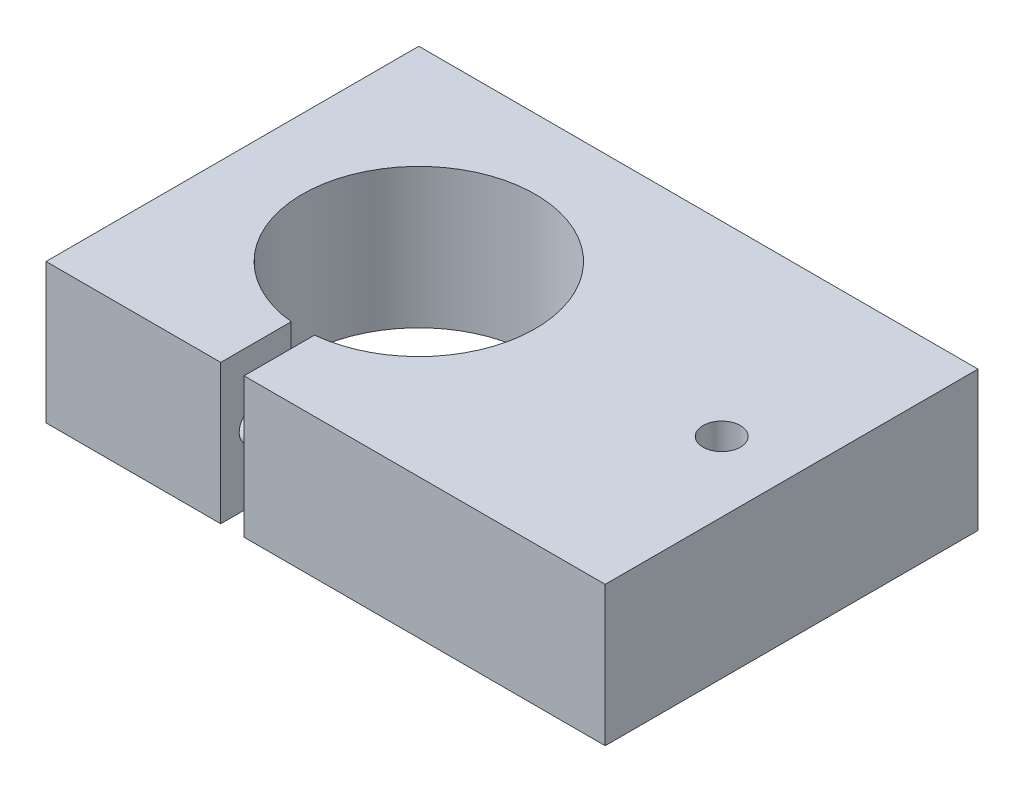
SolidWorks part; units mm, degrees
ref_plane "Front Plane" through (0, 0, 0) normal (0, 0, 1) x (1, 0, 0)
ref_plane "Top Plane" through (0, 0, 0) normal (0, 1, 0) x (1, 0, 0)
ref_plane "Right Plane" through (0, 0, 0) normal (1, 0, 0) x (0, 0, -1)
sketch "Sketch1" plane through (0, 0, 0) normal (0, 1, 0) x (1, 0, 0)
  line L1 (-38.1, -25.4) -> (38.1, -25.4)
  line L2 (-38.1, -25.4) -> (-38.1, 25.4)
  line L3 (-38.1, 25.4) -> (38.1, 25.4)
  line L4 (38.1, -25.4) -> (38.1, 25.4)
  line L5 (-38.1, -25.4) -> (38.1, 25.4) construction
  line L6 (-38.1, 25.4) -> (38.1, -25.4) construction
  point P0 (0, 0)
  dimension "D1" = 76.2
  dimension "D2" = 50.8
extrude "Boss-Extrude1" add sketch "Sketch1" along normal mid plane 19.05 contours L1 L4 L3 L2
sketch "Sketch2" plane through (0, 9.525, 0) normal (0, 1, 0) x (1, 0, 0)
  line L0 (-55, 0) -> (55, 0) construction
  line L2 (-38.1, -25.4) -> (-38.1, 25.4) construction
  circle A0 centre (-12.7, 0) radius 15.875
  dimension "D1" = 31.75
  dimension "D2" = 25.4
extrude "Cut-Extrude1" cut sketch "Sketch2" against normal through all
sketch "Sketch3" plane through (0, 9.525, 0) normal (0, 1, 0) x (1, 0, 0)
  line L1 (-11.1125, -28.0194) -> (-14.2875, -28.0194)
  line L2 (-11.1125, -28.0194) -> (-11.1125, 0)
  line L3 (-11.1125, 0) -> (-14.2875, 0)
  line L4 (-14.2875, -28.0194) -> (-14.2875, 0)
  line L5 (-11.1125, -28.0194) -> (-14.2875, 0) construction
  line L6 (-11.1125, 0) -> (-14.2875, -28.0194) construction
  point P0 (-12.7, -14.0097)
  point P5 (0, 0)
  point P6 (-12.7, 0)
  point P7 (-12.7, 0)
  dimension "D1" = 3.175
extrude "Cut-Extrude2" cut sketch "Sketch3" against normal through all
sketch "Sketch4" plane through (-38.1, 0, 0) normal (-1, 0, 0) x (0, 0, 1)
  line L0 (55, 0) -> (-55, 0) construction
  line L1 (25.4, 9.525) -> (25.4, -9.525) construction
  point P0 (20.6375, 0)
  dimension "D1" = 4.7625
hole_wizard "CBORE for #8 Socket Head Cap Screw1" positions "Sketch5" profile "Sketch7" counterbore size "#8" standard "ANSI Inch" end condition up to next
sketch "Sketch5" plane through (-38.1, 0, 0) normal (-1, 0, 0) x (0, 0, 1)
  point P0 (20.6375, 0)
sketch "Sketch7" plane through (-38.1, 0, 20.6375) normal (0, 1, 0) x (0, 0, 1)
  line L0 (0, 0) -> (0, 23.8125)
  line L1 (0, 23.8125) -> (2.2479, 23.8125)
  line L3 (2.2479, 23.8125) -> (2.2479, 4.1656)
  line L4 (2.2479, 4.1656) -> (3.9687, 4.1656)
  line L5 (3.9687, 4.1656) -> (3.9687, 0)
  line L7 (3.9687, 0) -> (0, 0)
  line L11 (0, -6.35) -> (0, 107.95) construction
  dimension "Thru Hole Dia." = 4.4958
  dimension "Thru Hole Depth" = 23.8125
  dimension "C'Bore Dia." = 7.9375
  dimension "C'Bore Depth" = 4.1656
hole_wizard "#8-32 Tapped Hole1" positions "Sketch8" profile "Sketch10" tap size "#8-32" standard "ANSI Inch"
sketch "Sketch8" plane through (-11.1125, 0, 0) normal (-1, 0, 0) x (0, 0, 1)
  point P0 (20.6375, 0)
cosmetic thread "Hole Thread1" parameters "D1"=36.576, "D2"=4.1656
sketch "Sketch10" plane through (-11.1125, 0, 20.6375) normal (0, 1, 0) x (0, 0, 1)
  line L0 (0, 0) -> (0, 13.7378)
  line L1 (0, 13.7378) -> (1.7272, 12.7)
  line L2 (1.7272, 12.7) -> (1.7272, 0)
  line L5 (1.7272, 0) -> (0, 0)
  line L10 (0, 13.7378) -> (-1.7272, 12.7) construction
  line L11 (0, -6.35) -> (0, 107.95) construction
  dimension "Tap Drill Dia." = 3.4544
  dimension "Tap Drill Depth" = 12.7
  dimension "Drill Angle" = 118
sketch "Sketch11" plane through (0, 9.525, 0) normal (0, 1, 0) x (1, 0, 0)
  line L0 (-55, 0) -> (55, 0) construction
  line L1 (38.1, -25.4) -> (38.1, 25.4) construction
  point P0 (28.575, 0)
  dimension "D1" = 9.525
hole_wizard "1/4-20 Tapped Hole1" positions "Sketch12" profile "Sketch13" tap size "1/4-20" standard "ANSI Inch" end condition through all
sketch "Sketch12" plane through (0, 9.525, 0) normal (0, 1, 0) x (1, 0, 0)
  point P0 (28.575, 0)
cosmetic thread "Hole Thread2" parameters "D2"=6.35
sketch "Sketch13" plane through (28.575, 9.525, 0) normal (1, 0, 0) x (0, 0, 1)
  line L0 (0, 0) -> (0, 19.05)
  line L1 (0, 19.05) -> (2.5527, 19.05)
  line L2 (2.5527, 19.05) -> (2.5527, 0)
  line L5 (2.5527, 0) -> (0, 0)
  line L11 (0, -6.35) -> (0, 107.95) construction
  dimension "Thru Tap Drill Dia." = 5.1054
  dimension "Thru Tap Drill Depth" = 19.05
